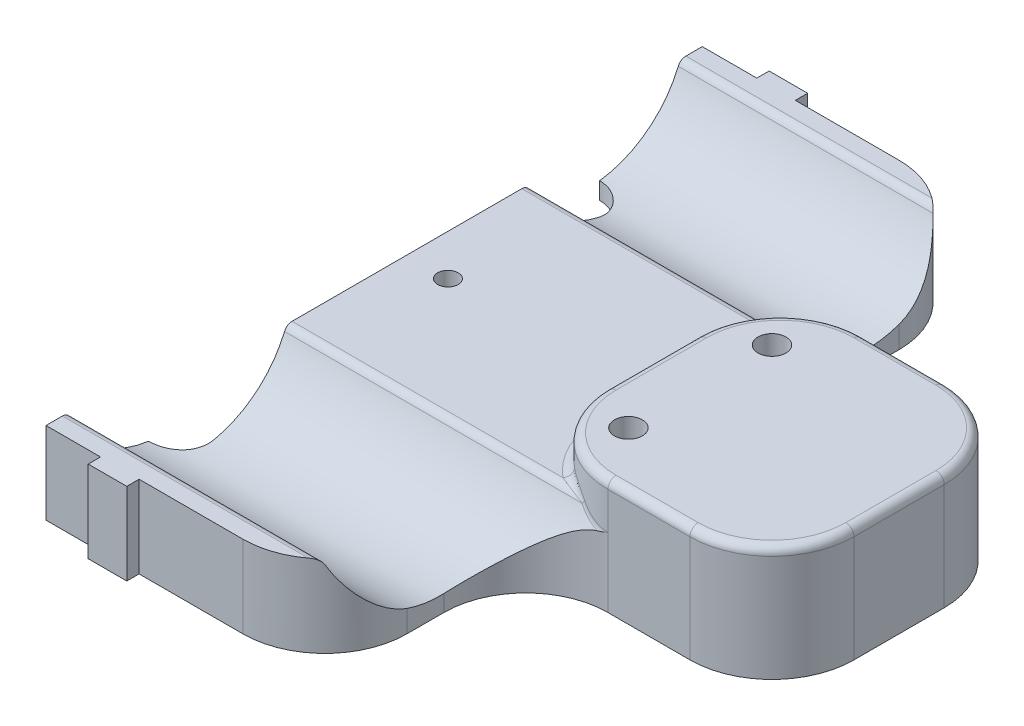
SolidWorks part; units mm, degrees
ref_plane "Plan de face" through (0, 0, 0) normal (0, 0, 1) x (1, 0, 0)
ref_plane "Plan de dessus" through (0, 0, 0) normal (0, 1, 0) x (1, 0, 0)
ref_plane "Plan de droite" through (0, 0, 0) normal (1, 0, 0) x (0, 0, -1)
sketch "Esquisse1" plane through (0, 0, 0) normal (0, 1, 0) x (1, 0, 0)
  line L0 (0, 50) -> (0, -50) construction
  line L1 (-9, 40) -> (-9, -40)
  line L2 (-10, 60) -> (10, 60) construction
  line L3 (-10, 60) -> (-10, 40) construction
  line L4 (-10, 40) -> (10, 40) construction
  line L5 (10, 60) -> (10, 40) construction
  line L6 (-10, 60) -> (10, 40) construction
  line L7 (-10, 40) -> (10, 60) construction
  line L8 (-10, -40) -> (10, -40) construction
  line L9 (-10, -40) -> (-10, -60) construction
  line L10 (-10, -60) -> (10, -60) construction
  line L11 (10, -40) -> (10, -60) construction
  line L12 (-10, -40) -> (10, -60) construction
  line L13 (-10, -60) -> (10, -40) construction
  line L14 (-9, -40) -> (-2.35, -40)
  line L15 (-2.35, -40) -> (-2.35, -41.5)
  line L16 (-2.35, -41.5) -> (2.35, -41.5)
  line L17 (2.35, -41.5) -> (2.35, -40)
  line L18 (2.35, -40) -> (25, -40)
  line L19 (25, -40) -> (25, -15.5)
  line L20 (25, -15.5) -> (55, -15.5)
  line L21 (55, -15.5) -> (55, 15.5)
  line L22 (55, 15.5) -> (25, 15.5)
  line L23 (25, 15.5) -> (25, 40)
  line L24 (25, 40) -> (2.35, 40)
  line L25 (2.35, 40) -> (2.35, 41.5)
  line L26 (2.35, 41.5) -> (-2.35, 41.5)
  line L27 (-2.35, 41.5) -> (-2.35, 40)
  line L28 (-2.35, 40) -> (-9, 40)
  line L29 (25, 15.5) -> (25, -15.5) construction
  line L30 (0, 0) -> (25, 0) construction
  point P4 (0, 0)
  point P15 (0, 41.5)
  point P30 (0, -41.5)
  dimension "D1" = 100
  dimension "D2" = 20
  dimension "D3" = 4.7
  dimension "D4" = 1.5
  dimension "D5" = 1
  dimension "D6" = 15
  dimension "D7" = 31
  dimension "D8" = 30
extrude "Boss.-Extru.1" add sketch "Esquisse1" along normal blind 10 contours L24 L25 L26 L27 L28 L1 L14 L15 L16 L17 L18 L19 L20 L21 L22 L23
sketch "Esquisse2" plane through (-9, 0, 0) normal (-1, 0, 0) x (0, 0, 1)
  line L0 (-40, 0) -> (40, 0) construction
  line L1 (-40, 10) -> (-40, 0) construction
  line L2 (0, -5.5) -> (0, 5.5) construction
  circle A0 centre (-26, 14) radius 12
  circle A1 centre (26, 14) radius 12
  dimension "D1" = 24
  dimension "D2" = 2
  dimension "D3" = 2
extrude "Enlèv. mat.-Extru.1" cut sketch "Esquisse2" against normal up to surface (34 mm away) up to face at (25, 5, 27.75)
sketch "Esquisse7" plane through (0, 10, 0) normal (0, 1, 0) x (1, 0, 0)
  line L1 (55, 15.5) -> (25, 15.5)
  line L2 (55, 15.5) -> (55, -15.5)
  line L3 (55, -15.5) -> (25, -15.5)
  line L4 (25, 15.5) -> (25, -15.5)
extrude "Boss.-Extru.2" add sketch "Esquisse7" along normal blind 4
hole_wizard "Dégagement M31" positions "Esquisse4" profile "Esquisse5" hole size "M3" standard "Ansi Metric" end condition through all
sketch "Esquisse4" plane through (0, 14, 0) normal (0, 1, 0) x (1, 0, 0)
  line L0 (0, 0) -> (30.75, 0) construction
  line L2 (30.75, 8.75) -> (30.75, -8.75) construction
  point P6 (30.75, 8.75)
  point P7 (30.75, -8.75)
  point P10 (30.75, 0)
  dimension "D1" = 30.75
  dimension "D2" = 17.5
sketch "Esquisse5" plane through (30.75, 14, 8.75) normal (1, 0, 0) x (0, 0, 1)
  line L0 (0, 0) -> (0, 14)
  line L1 (0, 14) -> (1.7, 14)
  line L2 (1.7, 14) -> (1.7, 0)
  line L5 (1.7, 0) -> (0, 0)
  line L11 (0, -6.35) -> (0, 107.95) construction
  dimension "Diamètre du perçage jusqu'au prochain" = 3.4
  dimension "Profondeur du perçage jusqu'au prochain" = 14
sketch "Esquisse6" plane through (0, 0, 0) normal (0, -1, 0) x (1, 0, 0)
  line L0 (-9, -40) -> (-9, 40) construction
  line L1 (-9, -27.5) -> (-5, -27.5)
  line L2 (-9, -27.5) -> (-9, 27.5)
  line L3 (-9, 27.5) -> (-5, 27.5)
  line L4 (-5, -27.5) -> (-5, 27.5)
  line L5 (2.35, -41.5) -> (-2.35, -41.5) construction
  line L6 (-2.35, -40) -> (-9, -40) construction
  line L7 (0, 0) -> (-5, 0) construction
  point P8 (0, -41.5)
  dimension "D1" = 5
  dimension "D2" = 12.5
extrude "Enlèv. mat.-Extru.2" cut sketch "Esquisse6" against normal up to next
fillet "Congé1" radius 4 2 edges at (-5, 1.0471, 27.5) (-5, 1.0471, -27.5)
fillet "Congé2" radius 10 6 edges at (25, 4.0953, -15.5) (25, 4.0953, 15.5) (55, 7, -15.5) (55, 7, 15.5) (25, 5, -40) (25, 5, 40)
fillet "Congé4" radius 10 2 edges at (25, 11.0953, -15.5) (25, 11.0953, 15.5)
fillet "Congé5" radius 1 17 edges at (32.279, 8.932, -15.1227) (26.648, 10, -10.9995) (25, 10, 0) (26.648, 10, 10.9995) (27.9289, 14, 12.5711) (25, 14, 0) (27.9289, 14, -12.5711) (40, 14, -15.5) (52.0711, 14, -12.5711) (55, 14, 0) (52.0711, 14, 12.5711) (33.3489, 8.4458, 15.3628) (13.0244, 10, -14.6863) (13.0244, 10, 14.6863) (40, 14, 15.5) (6.4099, 10, 37.3137) (6.4099, 10, -37.3137)
sketch "Esquisse8" plane through (0, 0, 0) normal (0, -1, 0) x (1, 0, 0)
  line L1 (27.5746, -8.75) -> (29.1623, -11.5)
  line L2 (29.1623, -11.5) -> (32.3377, -11.5)
  line L3 (32.3377, -11.5) -> (33.9254, -8.75)
  line L4 (33.9254, -8.75) -> (32.3377, -6)
  line L5 (32.3377, -6) -> (29.1623, -6)
  line L6 (29.1623, -6) -> (27.5746, -8.75)
  line L7 (27.5746, 8.75) -> (29.1623, 6)
  line L8 (29.1623, 6) -> (32.3377, 6)
  line L9 (32.3377, 6) -> (33.9254, 8.75)
  line L10 (33.9254, 8.75) -> (32.3377, 11.5)
  line L11 (32.3377, 11.5) -> (29.1623, 11.5)
  line L12 (29.1623, 11.5) -> (27.5746, 8.75)
  circle A0 centre (30.75, -8.75) radius 2.75 construction
  circle A1 centre (30.75, 8.75) radius 2.75 construction
  dimension "D1" = 5.5
extrude "Enlèv. mat.-Extru.3" cut sketch "Esquisse8" against normal blind 4
hole_wizard "Trou pour taraudage pour trou taraudé M3x0.51" positions "Esquisse9" profile "Esquisse10" hole size "M3x0.5" standard "Ansi Metric" end condition through all
sketch "Esquisse9" plane through (0, 10, 0) normal (0, 1, 0) x (1, 0, 0)
  point P0 (0, 0)
sketch "Esquisse10" plane through (0, 10, 0) normal (1, 0, 0) x (0, 0, 1)
  line L0 (0, 0) -> (0, 10)
  line L1 (0, 10) -> (1.25, 10)
  line L2 (1.25, 10) -> (1.25, 0)
  line L5 (1.25, 0) -> (0, 0)
  line L11 (0, -6.35) -> (0, 107.95) construction
  dimension "Diamètre du perçage jusqu'au prochain" = 2.5
  dimension "Profondeur du perçage jusqu'au prochain" = 10
